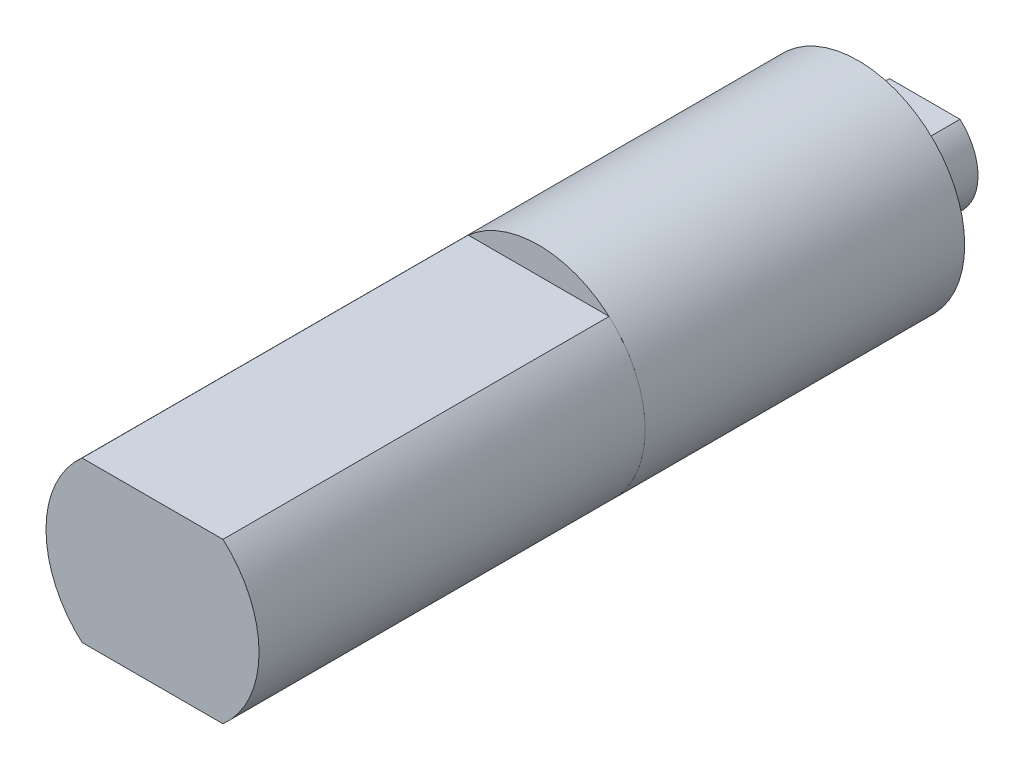
SolidWorks part; units mm, degrees
ref_plane "Front Plane" through (0, 0, 0) normal (0, 0, 1) x (1, 0, 0)
ref_plane "Top Plane" through (0, 0, 0) normal (0, 1, 0) x (1, 0, 0)
ref_plane "Right Plane" through (0, 0, 0) normal (1, 0, 0) x (0, 0, -1)
sketch "Sketch1" plane through (0, 0, 0) normal (0, 0, 1) x (1, 0, 0)
  circle A0 centre (0, 0) radius 2
  circle A1 centre (0, 0) radius 4
  dimension "D1" = 8
  dimension "D2" = 4
extrude "Boss-Extrude1" add sketch "Sketch1" along normal blind 12 contours A0 | A1 A0 region at (0, 0, 0) region at (-3.8869, 0, 0)
extrude "Boss-Extrude2" add sketch "Sketch1<4>" against normal blind 2.5 contours A0 region at (0, 0, 0)
sketch "Sketch1<4>" plane through (0, 0, 0) normal (0, 0, 1) x (1, 0, 0) same geometry as "Sketch1"
sketch "Sketch2" plane through (0, 0, 12) normal (0, 0, 1) x (1, 0, 0)
  line L0 (0, 5.4886) -> (0, -5.4886) construction
  line L1 (-4, -3) -> (-2.6458, -3) construction
  line L2 (-2.6458, 3) -> (2.6458, 3)
  line L3 (-4, 3) -> (-4, 0) construction
  line L4 (-2.6458, -3) -> (2.6458, -3)
  line L5 (4, 3) -> (4, 0) construction
  line L6 (0, -3) -> (0, 3) construction
  line L7 (-4, 0) -> (4, 0) construction
  line L8 (-4, 0) -> (-4, -3) construction
  line L9 (-4, 3) -> (-2.6458, 3) construction
  line L10 (2.6458, 3) -> (4, 3) construction
  line L11 (2.6458, -3) -> (4, -3) construction
  line L12 (4, 0) -> (4, -3) construction
  arc A0 (2.6458, -3) -> (2.6458, 3) centre (0, 0) ccw
  arc A1 (-2.6458, -3) -> (0, -4) centre (0, 0) ccw construction
  arc A2 (0, -4) -> (2.6458, -3) centre (0, 0) ccw construction
  arc A3 (-2.6458, 3) -> (-2.6458, -3) centre (0, 0) ccw
  arc A4 (2.6458, 3) -> (0, 4) centre (0, 0) ccw construction
  arc A5 (0, 4) -> (-2.6458, 3) centre (0, 0) ccw construction
  point P2 (0, 0)
  point P5 (0, 0)
  dimension "D1" = 8
  dimension "D2" = 8
  dimension "D3" = 6
extrude "Boss-Extrude3" add sketch "Sketch2" along normal blind 14.5 separate body
sketch "Sketch3" plane through (0, 0, -2.5) normal (0, 0, -1) x (-1, 0, 0)
  line L0 (-1.3229, 1.5) -> (1.3229, 1.5)
  circle A0 centre (0, 0) radius 2
  circle A3 centre (0, 0) radius 2 construction
  point P11 (0, 1.5)
  circle M2 centre (0, 0) radius 2
  dimension "D1" = 1.5
extrude "Cut-Extrude1" cut sketch "Sketch3" against normal blind 2.5 contours L0 M2 region at (0, 1.7023, -2.5)
